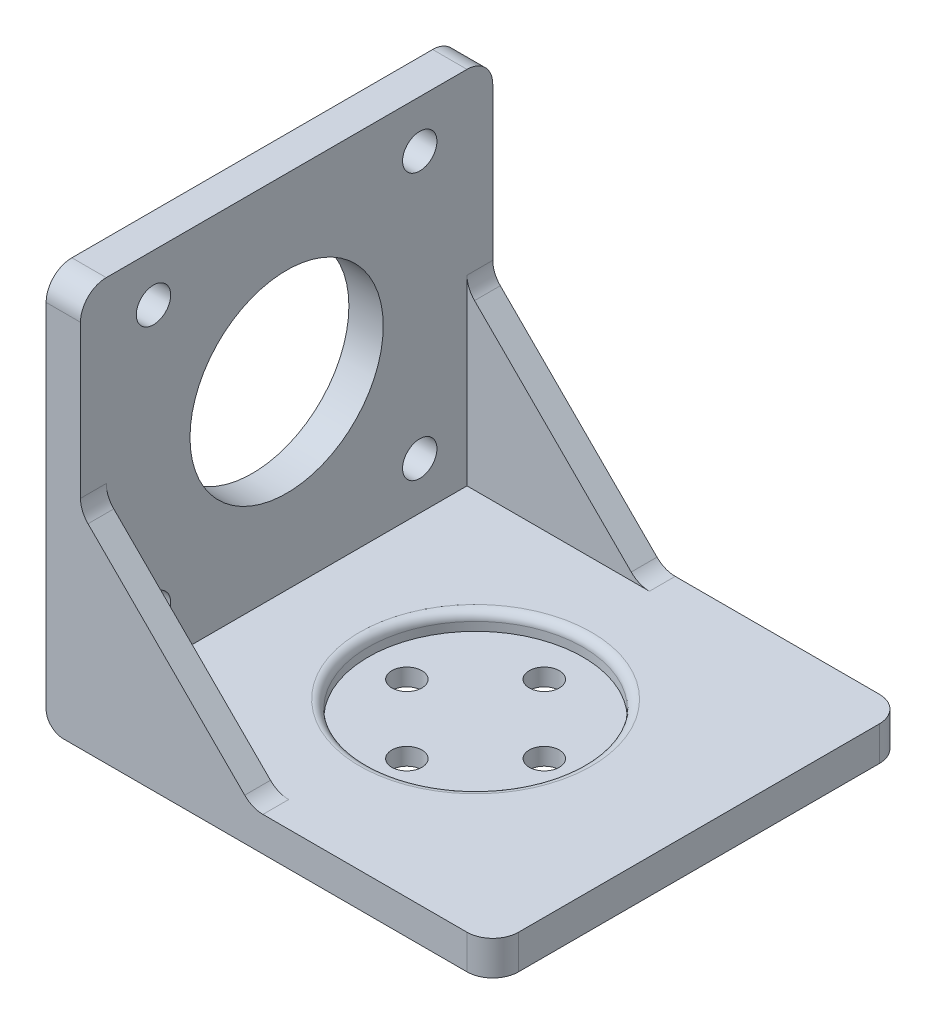
SolidWorks part; units mm, degrees
ref_plane "前视基准面" through (0, 0, 0) normal (0, 0, 1) x (1, 0, 0)
ref_plane "上视基准面" through (0, 0, 0) normal (0, 1, 0) x (1, 0, 0)
ref_plane "右视基准面" through (0, 0, 0) normal (1, 0, 0) x (0, 0, -1)
other "Configuration Table"
sketch "草图1" plane through (0, 0, 0) normal (0, 1, 0) x (1, 0, 0)
  line L1 (-26, -21) -> (26, -21)
  line L2 (-26, -21) -> (-26, 21)
  line L3 (-26, 21) -> (26, 21)
  line L4 (26, -21) -> (26, 21)
  line L5 (-26, -21) -> (26, 21) construction
  line L6 (-26, 21) -> (26, -21) construction
  circle A0 centre (8, 0) radius 1.75
  circle A1 centre (0, 8) radius 1.75
  circle A2 centre (-8, 0) radius 1.75
  circle A3 centre (0, -8) radius 1.75
  point P0 (0, 0)
  dimension "D3" = 3.5
  dimension "D10" = 3.5
  dimension "D11" = 3.5
  dimension "D13" = 3.5
  dimension "D1" = 42
  dimension "D2" = 52
  dimension "D4" = 16
  dimension "D5" = 16
  dimension "D6" = 0
  dimension "D7" = 0
  dimension "D8" = 13
  dimension "D9" = 26
  dimension "D12" = 18
  dimension "D14" = 21
extrude "凸台-拉伸2" add sketch "草图1" along normal blind 4
sketch "草图2" plane through (-26, 0, 0) normal (-1, 0, 0) x (0, 0, 1)
  line L0 (21, 4) -> (-21, 4)
  line L1 (21, 4) -> (21, 46)
  line L2 (-21, 4) -> (-21, 46)
  line L3 (21, 46) -> (-21, 46)
  circle A0 centre (15.5, 40.5) radius 2
  circle A1 centre (15.5, 9.5) radius 2
  circle A2 centre (-15.5, 9.5) radius 2
  circle A3 centre (-15.5, 40.5) radius 2
  circle A4 centre (0, 25) radius 11.25
  dimension "D2" = 4
  dimension "D3" = 4
  dimension "D4" = 4
  dimension "D5" = 4
  dimension "D14" = 22.5
  dimension "D1" = 42
  dimension "D6" = 31
  dimension "D7" = 31
  dimension "D8" = 31
  dimension "D9" = 5.5
  dimension "D10" = 5.5
  dimension "D11" = 0
  dimension "D12" = 0
  dimension "D13" = 0
  dimension "D15" = 21
  dimension "D16" = 21
extrude "凸台-拉伸3" add sketch "草图2" against normal blind 4
sketch "草图4" plane through (0, 4, 0) normal (0, 1, 0) x (1, 0, 0)
  circle A0 centre (0, 0) radius 12.5
  dimension "D1" = 25
extrude "切除-拉伸1" cut sketch "草图4" against normal blind 2
sketch "草图6" plane through (0, 0, 21) normal (0, 0, 1) x (1, 0, 0)
  line L0 (-26, 46) -> (-22, 46)
  line L1 (-22, 46) -> (-22, 24)
  line L2 (-22, 4) -> (-22, 46) construction
  line L3 (-22, 24) -> (-2, 4)
  line L4 (-22, 4) -> (26, 4) construction
  line L5 (-2, 4) -> (26, 4)
  line L6 (26, 4) -> (26, 0)
  line L7 (26, 0) -> (-26, 0)
  line L8 (-26, 0) -> (-26, 46)
  dimension "D1" = 20
  dimension "D2" = 20
extrude "凸台-拉伸4" add sketch "草图6" along normal blind 3 contours L8 L0 L1 L3 L5 L6 L7
sketch "草图7" plane through (0, 0, -21) normal (0, 0, -1) x (-1, 0, 0)
  line L0 (26, 46) -> (26, 0)
  line L1 (26, 0) -> (-26, 0)
  line L2 (-26, 0) -> (-26, 4)
  line L3 (-26, 4) -> (2, 4)
  line L4 (-26, 4) -> (22, 4) construction
  line L5 (22, 4) -> (2, 4) construction
  line L6 (2, 4) -> (22, 24)
  line L7 (22, 46) -> (22, 4) construction
  line L8 (22, 4) -> (22, 24) construction
  line L9 (22, 24) -> (22, 46)
  line L10 (22, 46) -> (26, 46) construction
  line L11 (22, 46) -> (26, 46)
  dimension "D1" = 20
  dimension "D2" = 20
extrude "凸台-拉伸5" add sketch "草图7" along normal blind 3
fillet "圆角1" radius 3 1 edges at (-24, 46, 24)
fillet "圆角2" radius 3 1 edges at (-24, 46, -24)
fillet "圆角3" radius 3 1 edges at (26, 2, 24)
fillet "圆角4" radius 3 1 edges at (26, 2, -24)
fillet "圆角5" radius 3 1 edges at (-22, 24, 22.5)
fillet "圆角6" radius 3 1 edges at (-2, 4, 22.5)
fillet "圆角7" radius 3 1 edges at (-22, 24, -22.5)
fillet "圆角8" radius 3 1 edges at (-2, 4, -22.5)
fillet "圆角9" radius 1 1 edges at (0, 4, 12.5)
fillet "圆角10" radius 2 1 edges at (-26, 0, 0)
